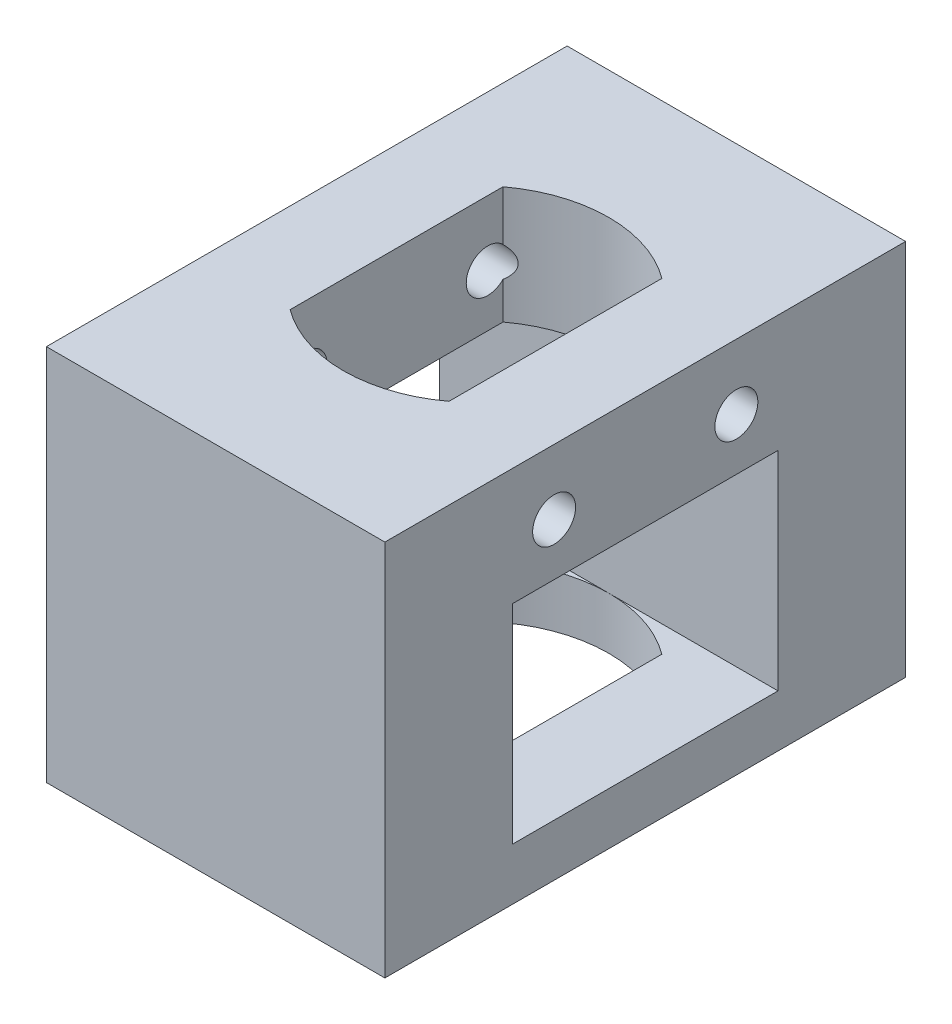
SolidWorks part; units mm, degrees
ref_plane "Front Plane" through (0, 0, 0) normal (0, 0, 1) x (1, 0, 0)
ref_plane "Top Plane" through (0, 0, 0) normal (0, 1, 0) x (1, 0, 0)
ref_plane "Right Plane" through (0, 0, 0) normal (1, 0, 0) x (0, 0, -1)
sketch "Sketch1" plane through (0, 0, 0) normal (0, 1, 0) x (1, 0, 0)
  line L0 (0, -419.7539) -> (0, 20567.943) construction
  line L1 (6.1, 8.175) -> (6.1, -8.175)
  line L2 (-6.1, 8.175) -> (-6.1, -8.175)
  line L4 (-13, -20) -> (13, -20)
  line L5 (-13, -20) -> (-13, 20)
  line L6 (-13, 20) -> (13, 20)
  line L7 (13, -20) -> (13, 20)
  line L8 (0, 20) -> (0, -20) construction
  line L9 (-13, 0) -> (13, 0) construction
  arc A0 (6.1, 8.175) -> (-6.1, 8.175) centre (0, 0) ccw
  arc A1 (-6.1, -8.175) -> (6.1, -8.175) centre (0, 0) ccw
  dimension "D1" = 20.4
  dimension "D2" = 12.2
  dimension "D3" = 40
  dimension "D4" = 26
extrude "Boss-Extrude1" add sketch "Sketch1" against normal blind 29 contours L4 L7 L6 L5 A1 L2 A0 L1 region at (-12.5229, 0, 0)
sketch "Sketch2" plane through (0, 0, 0) normal (1, 0, 0) x (0, 0, -1)
  line L0 (0, -1000) -> (0, 49000) construction
  line L1 (-20, 0) -> (20, 0) construction
  line L2 (10.2, -25) -> (10.2, -9)
  line L3 (-10.2, -25) -> (-10.2, -9)
  line L4 (-10.2, -25) -> (10.2, -25)
  line L5 (-10.2, -9) -> (10.2, -9)
  circle A0 centre (7, -5) radius 1.65
  circle A1 centre (-7, -5) radius 1.65
  dimension "D1" = 3.3
  dimension "D2" = 5
  dimension "D3" = 14
  dimension "D4" = 20
  dimension "D5" = 16
  dimension "D6" = 20.4
extrude "Cut-Extrude1" cut sketch "Sketch2" against normal through all both and the other way through all contours A1 | A0 | L4 L0 L5 L3 | L0 L4 L2 L5 region at (0, -17, 5.1) region at (0, -17, -5.1) region at (0, -5, -7) region at (0, -5, 7)
ref_plane "Plane1" through (16, 0, 0) normal (1, 0, 0) x (0, 0, -1)
sketch "Sketch3" plane through (16, 0, 0) normal (1, 0, 0) x (0, 0, -1)
  line L0 (-10.2, -9) -> (10.2, -9) construction
  line L1 (-20, -29) -> (20, -29)
  line L2 (-20, -29) -> (-20, 11)
  line L3 (-20, 11) -> (20, 11)
  line L4 (20, -29) -> (20, 11)
  line L5 (0, 11) -> (0, -29) construction
  line L6 (-20, -9) -> (20, -9) construction
  line L7 (-20, 11) -> (-20, 51)
  line L8 (-16, -25) -> (16, -25) construction
  line L9 (-16, -25) -> (-16, 7) construction
  line L10 (-16, 7) -> (16, 7) construction
  line L11 (16, -25) -> (16, 7) construction
  line L12 (0, 7) -> (0, -25) construction
  line L13 (-16, -9) -> (16, -9) construction
  line L14 (-20, 51) -> (20, 51)
  line L15 (20, 51) -> (20, 11)
  line L17 (-17.5, 13.5) -> (17.5, 13.5) construction
  line L18 (-17.5, 13.5) -> (-17.5, 48.5) construction
  line L19 (-17.5, 48.5) -> (17.5, 48.5) construction
  line L20 (17.5, 13.5) -> (17.5, 48.5) construction
  line L21 (0, 48.5) -> (0, 13.5) construction
  line L22 (-17.5, 31) -> (17.5, 31) construction
  circle A0 centre (0, -9) radius 19
  circle A1 centre (-16, 7) radius 1.7
  circle A2 centre (16, 7) radius 1.7
  circle A3 centre (-16, -25) radius 1.7
  circle A4 centre (16, -25) radius 1.7
  circle A5 centre (-17.5, 48.5) radius 1.1
  circle A6 centre (17.5, 48.5) radius 1.1
  circle A7 centre (-17.5, 13.5) radius 1.1
  circle A8 centre (17.5, 13.5) radius 1.1
  point P0 (0, -9)
  point P15 (0, 31)
  dimension "D2" = 38
  dimension "D3" = 3.4
  dimension "D9" = 2.2
  dimension "D1" = 40
  dimension "D4" = 32
  dimension "D5" = 9
  dimension "D6" = 35
  dimension "D7" = 20
  dimension "D8" = 40
sketch "Sketch4" plane through (16, 0, 0) normal (1, 0, 0) x (0, 0, -1)
  line L0 (0, 11) -> (0, -29) construction
  circle A0 centre (0, -9) radius 19.9
  circle A1 centre (0, -9) radius 19 construction
  point P0 (0, -9)
  dimension "D1" = 39.8
  dimension "D2" = 0.9
sketch "Sketch5" plane through (6.1, 0, 0) normal (-1, 0, 0) x (0, 0, 1)
  line L0 (10.2, -25) -> (-10.2, -25) construction
  line L1 (10.2, -25) -> (10.2, -9) construction
  line L2 (10.2, -9) -> (-10.2, -9) construction
  line L3 (-10.2, -25) -> (-10.2, -9) construction
  line L4 (10.2, -25) -> (-10.2, -25) construction
  line L5 (10.2, -25) -> (10.2, -9) construction
  line L6 (10.2, -9) -> (-10.2, -9) construction
  line L7 (-10.2, -25) -> (-10.2, -9) construction
  line L8 (-12.6, -27.4) -> (-12.6, -6.6)
  line L9 (12.6, -6.6) -> (-12.6, -6.6)
  line L10 (12.6, -27.4) -> (12.6, -6.6)
  line L11 (12.6, -27.4) -> (-12.6, -27.4)
  dimension "D1" = 2.4
sketch "Sketch8" plane through (6.1, 0, 0) normal (-1, 0, 0) x (0, 0, 1)
  line L0 (10.2, -9) -> (-10.2, -9) construction
  line L1 (10.2, -9) -> (-10.2, -9)
  line L2 (-10.2, -9) -> (-20, -9)
  line L3 (10.2, -9) -> (20, -9)
  line L4 (20, 0) -> (-20, 0)
  line L5 (-20, 0) -> (-20, -29)
  line L6 (-20, -29) -> (20, -29)
  line L7 (20, -29) -> (20, 0)
  line L8 (20, 0) -> (-20, 0)
  line L9 (-20, 0) -> (-20, -29)
  line L10 (-20, -29) -> (20, -29)
  line L11 (20, -29) -> (20, 0)
  circle A0 centre (7, -5) radius 1.65 construction
  circle A2 centre (7, -5) radius 1.65
  circle A3 centre (-7, -5) radius 1.65 construction
  circle A4 centre (-7, -5) radius 1.65
  circle A5 centre (-7, -5) radius 2.85
  circle A6 centre (7, -5) radius 2.85
  line M6 (8.175, -9) -> (8.175, -6.1584)
  arc M7 (8.175, -6.1584) -> (8.175, -3.8416) centre (7, -5) cw
  arc M9 (8.175, -6.1584) -> (8.175, -3.8416) centre (7, -5) cw
  line M10 (8.175, -3.8416) -> (8.175, 0)
  line M11 (8.175, 0) -> (-8.175, 0)
  line M12 (-8.175, 0) -> (-8.175, -3.8416)
  arc M13 (-8.175, -3.8416) -> (-8.175, -6.1584) centre (-7, -5) cw
  arc M15 (-8.175, -3.8416) -> (-8.175, -6.1584) centre (-7, -5) cw
  line M16 (-8.175, -6.1584) -> (-8.175, -9)
  dimension "D2" = 5.7
  dimension "D1" = 0
extrude "Boss-Extrude2" add sketch "Sketch8" against normal blind 4 contours A2 L1 L3 L11 L8 M6 M10 | A4 A2 M15 M16 M6 M7 M9 M10 M11 M12 M13 | A4 L8 L9 L2 L1 M12 M16 | A5 A4 M16 M12 M13 M15 | A5 A4 M12 M16 | A6 A2 M10 M6 M7 M9 | A6 A2 M6 M10 region at (6.1, -4.4688, 14.4136) region at (6.1, -4.3227, 0) region at (6.1, -4.4688, -14.4136) region at (6.1, -5, 8.934) region at (6.1, -5, 4.2198) region at (6.1, -6.8775, -8.1052) region at (6.1, -5, -8.934)
extrude "Boss-Extrude3" [suppressed] add sketch "Sketch3" against normal blind 3 contours A0 | L1 L4 L3 L2 A4 A3 A2 A1 A0
sketch "Sketch6" plane through (6.1, 0, 0) normal (-1, 0, 0) x (0, 0, 1)
  line L0 (-10.2, -25) -> (-10.2, -9) construction
  line L1 (10.2, -25) -> (-10.2, -25) construction
  line L2 (10.2, -25) -> (10.2, -9) construction
  line L3 (10.2, -9) -> (-10.2, -9) construction
  line L4 (-10.2, -25) -> (-10.2, -9)
  line L5 (10.2, -25) -> (-10.2, -25)
  line L6 (10.2, -25) -> (10.2, -9)
  line L7 (10.2, -9) -> (-10.2, -9)
sketch "Sketch7" plane through (16, 0, 0) normal (1, 0, 0) x (0, 0, -1)
  circle A0 centre (0, -9) radius 19
  circle A1 centre (0, -9) radius 19 construction
loft "Cut-Loft1" [suppressed] cut profiles "Sketch6", "Sketch7"
sketch "Sketch9" plane through (0, 0, 0) normal (0, 0, 1) x (1, 0, 0)
  line L0 (0, -1000) -> (0, 49000) construction
  circle A0 centre (0, 45) radius 10.15
  dimension "D1" = 20.3
  dimension "D2" = 45
sketch "Sketch10" plane through (-13, 0, 0) normal (-1, 0, 0) x (0, 0, 1)
  line L1 (-20, -29) -> (20, -29)
  line L2 (-20, -29) -> (-20, 11)
  line L3 (-20, 11) -> (20, 11)
  line L4 (20, -29) -> (20, 11)
  line L5 (-17.5, 8.5) -> (17.5, 8.5) construction
  line L6 (-17.5, 8.5) -> (-17.5, -26.5) construction
  line L7 (-17.5, -26.5) -> (17.5, -26.5) construction
  line L8 (17.5, 8.5) -> (17.5, -26.5) construction
  line L9 (0, -26.5) -> (0, 8.5) construction
  line L10 (-17.5, -9) -> (17.5, -9) construction
  circle A0 centre (-17.5, 8.5) radius 1.1
  circle A1 centre (17.5, 8.5) radius 1.1
  circle A2 centre (-17.5, -26.5) radius 1.1
  circle A3 centre (17.5, -26.5) radius 1.1
  point P5 (0, -9)
  point P7 (0, -9)
  dimension "D3" = 2.2
  dimension "D1" = 40
  dimension "D2" = 35
extrude "Boss-Extrude4" [suppressed] add sketch "Sketch10" along normal blind 3
